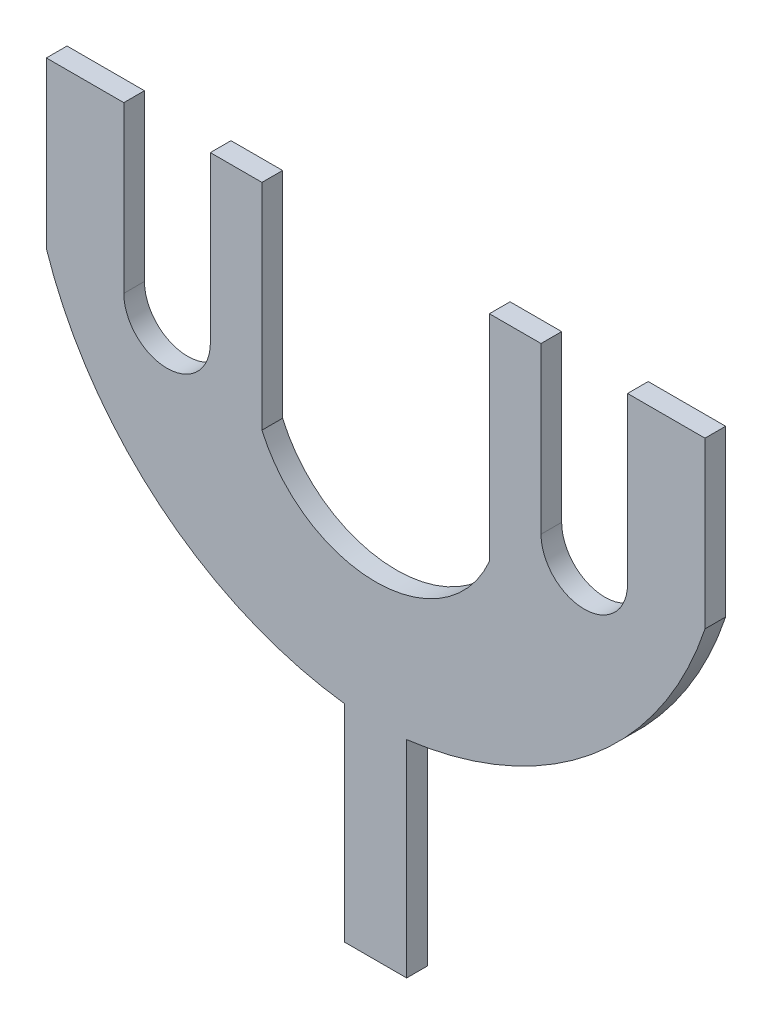
SolidWorks part; units mm, degrees
material "6061-T4 (SS)"
ref_plane "Front Plane" through (0, 0, 0) normal (0, 0, 1) x (1, 0, 0)
ref_plane "Top Plane" through (0, 0, 0) normal (0, 1, 0) x (1, 0, 0)
ref_plane "Right Plane" through (0, 0, 0) normal (1, 0, 0) x (0, 0, -1)
sketch "Sketch2" plane through (0, 0, 0) normal (0, 0, 1) x (1, 0, 0)
  line L0 (-20.895, 21.4878) -> (-17.145, 21.4878)
  line L1 (-20.895, 21.4878) -> (-20.895, 13.4878)
  line L2 (-10.455, 21.4878) -> (-10.455, 11.0954)
  line L3 (3.06, 21.4878) -> (3.06, 13.4878)
  line L4 (-20.895, 13.4878) -> (11, 13.4878) construction
  line L5 (11, 21.4878) -> (11, 8.9983) construction
  line L6 (-4.9475, 13.4878) -> (-4.9475, -8.3777) construction
  line L9 (-17.145, 13.4878) -> (-17.145, 21.4878)
  line L10 (11, 21.4878) -> (-25, 21.4878) construction
  line L13 (-12.955, 13.4878) -> (-12.955, 21.4878)
  line L14 (-12.955, 21.4878) -> (-10.455, 21.4878)
  line L16 (7.25, 13.4878) -> (7.25, 21.4878)
  line L17 (11, 13.4878) -> (11, 21.4878)
  line L23 (3.06, 21.4878) -> (0.56, 21.4878)
  line L24 (0.56, 21.4878) -> (0.56, 11.0954)
  line L25 (7.25, 21.4878) -> (11, 21.4878)
  line L28 (-6.4475, 1.6223) -> (-6.4475, -8.3777)
  line L29 (-6.4475, -8.3777) -> (-3.4475, -8.3777)
  line L30 (-3.4475, -8.3777) -> (-3.4475, 1.6223)
  arc A0 (-20.895, 13.4878) -> (-6.4475, 1.6223) centre (-4.2818, 18.9878) ccw
  arc A2 (-17.145, 13.4878) -> (-12.955, 13.4878) centre (-15.05, 13.4878) ccw
  arc A3 (3.06, 13.4878) -> (7.25, 13.4878) centre (5.155, 13.4878) ccw
  arc A4 (-10.455, 11.0954) -> (0.56, 11.0954) centre (-4.9475, 13.4878) ccw
  arc A5 (11, 13.4878) -> (-3.4475, 1.6223) centre (-5.6132, 18.9878) cw
  point P4 (-4.0657, 18.286)
  point P5 (-3.4475, 14.8616)
  point P9 (-3.4475, 14.8421)
  dimension "D1" = 2.5
  dimension "D9" = 17.5
  dimension "D10" = 17.5
  dimension "D2" = 2.5
  dimension "D3" = 10
  dimension "D4" = 4.19
  dimension "D5" = 5.5
  dimension "D6" = 3
  dimension "D7" = 3.75
  dimension "D8" = 3.75
extrude "Boss-Extrude2" add sketch "Sketch2" along normal blind 1
